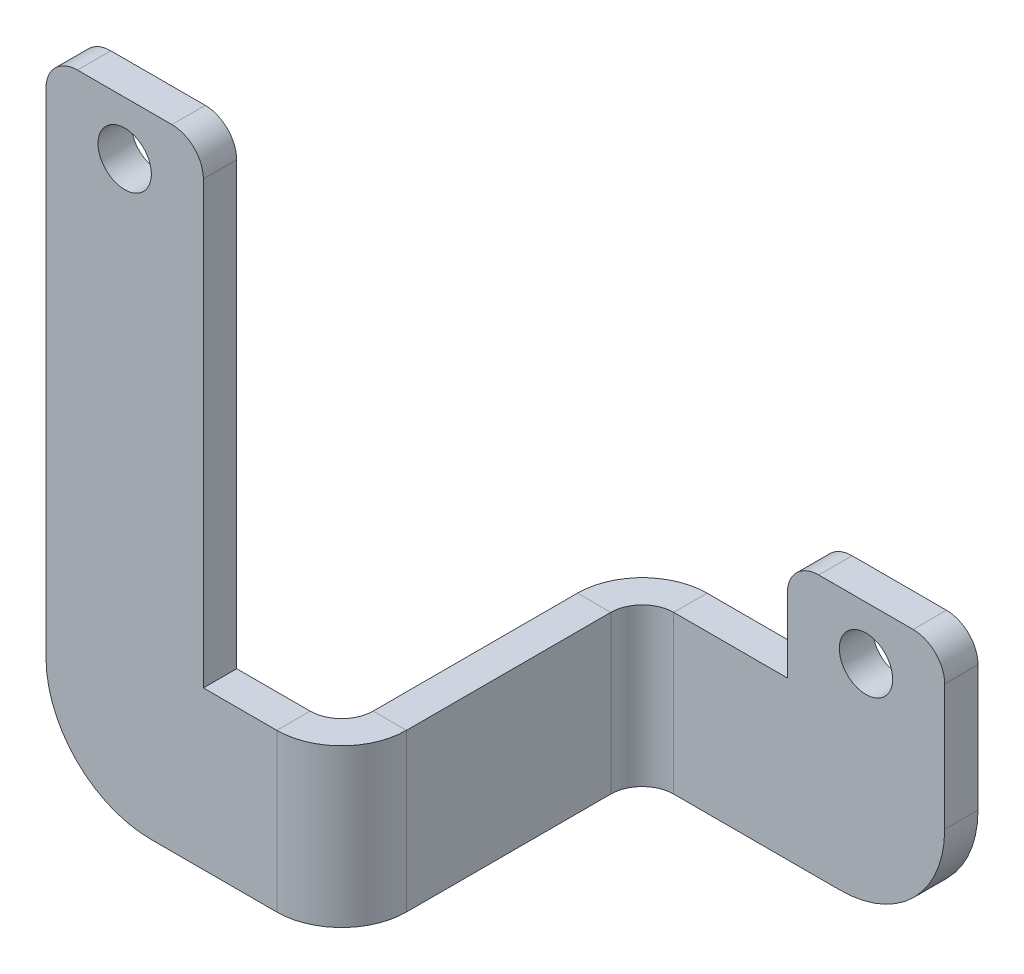
SolidWorks part; units mm, degrees
note: The reader was unsure of these and kept them because the rebuilt part matched: flange length of "Edge-Flange1", "Edge-Flange2".
material "Custom Plastic"
ref_plane "X-Y Datum" through (0, 0, 0) normal (0, 0, 1) x (1, 0, 0)
ref_plane "X-Z Datum" through (0, 0, 0) normal (0, 1, 0) x (1, 0, 0)
ref_plane "Y-Z Datum" through (0, 0, 0) normal (1, 0, 0) x (0, 0, -1)
sketch "Sketch1" plane through (0, 0, 0) normal (0, 0, 1) x (1, 0, 0)
  line L1 (-12.5, -7.5) -> (12.5, -7.5)
  line L2 (-12.5, -7.5) -> (-12.5, 7.5)
  line L3 (-12.5, 7.5) -> (12.5, 7.5)
  line L4 (12.5, -7.5) -> (12.5, 7.5)
  line L5 (-12.5, -7.5) -> (12.5, 7.5) construction
  line L6 (-12.5, 7.5) -> (12.5, -7.5) construction
  point P0 (0, 0)
  dimension "D1" = 25
  dimension "D2" = 15
base flange "Base-Flange1" sketch "Sketch1" thickness 3.175 reverse thickness direction no parameters "D1"=10
edge flange "Edge-Flange1" sketch "Sketch8" flange angle 90 flange length 28.65 flange position material outside bend radius 3 thickness 3.175 parameters "D6"=10
sketch "Sketch8" plane through (12.5, 0, -3.175) normal (-1, 0, 0) x (0, 1, 0)
  line L2 (-7.5, 0) -> (-7.5, 25.475)
  line L3 (-7.5, 25.475) -> (7.5, 25.475)
  line L4 (7.5, 25.475) -> (7.5, 0)
  line L5 (7.5, 0) -> (-7.5, 0) construction
  line L6 (7.5, 0) -> (-7.5, 0)
bend "EdgeBend1" bend radius 3 bend angle 90 parameters "D5"=1
edge flange "Edge-Flange2" sketch "Sketch11" flange angle 90 flange length 32 flange position material outside bend radius 3 thickness 3.175 parameters "D6"=10
sketch "Sketch11" plane through (15.675, 0, -28.65) normal (0, 0, 1) x (0, -1, 0)
  line L2 (-7.5, 0) -> (-7.5, 28.825)
  line L3 (-7.5, 28.825) -> (7.5, 28.825)
  line L4 (7.5, 28.825) -> (7.5, 0)
  line L5 (7.5, 0) -> (-7.5, 0) construction
  line L6 (7.5, 0) -> (-7.5, 0)
bend "EdgeBend2" bend radius 3 bend angle 90 parameters "D5"=2
sketch "Sketch12" plane through (0, 7.5, 0) normal (0, 1, 0) x (1, 0, 0)
  line L0 (9.5, 0) -> (-12.5, 0) construction
  line L1 (-12.5, 3.175) -> (2.5, 3.175)
  line L2 (-12.5, 3.175) -> (-12.5, 0)
  line L3 (-12.5, 0) -> (2.5, 0)
  line L4 (2.5, 3.175) -> (2.5, 0)
  dimension "D1" = 15
extrude "Boss-Extrude1" add sketch "Sketch12" along normal blind 45
sketch "Sketch15" plane through (0, 0, -3.175) normal (0, 0, -1) x (-1, 0, 0)
  line L0 (5, 52.5) -> (5, 47.42)
  line L3 (-2.5, 52.5) -> (12.5, 52.5) construction
  circle A2 centre (5, 47.42) radius 2.54
  dimension "D1" = 5.08
extrude "Cut-Extrude2" cut sketch "Sketch15" against normal through all
sketch "Sketch19" plane through (0, 7.5, 0) normal (0, 1, 0) x (1, 0, 0)
  line L0 (44.5, 28.65) -> (18.675, 28.65) construction
  line L1 (44.5, 31.825) -> (29.5, 31.825)
  line L2 (44.5, 31.825) -> (44.5, 28.65)
  line L3 (44.5, 28.65) -> (29.5, 28.65)
  line L4 (29.5, 31.825) -> (29.5, 28.65)
  dimension "D1" = 15
extrude "Boss-Extrude2" add sketch "Sketch19" along normal blind 10
sketch "Sketch21" plane through (0, 0, -31.825) normal (0, 0, -1) x (-1, 0, 0)
  line L0 (-37, 17.5) -> (-37, 12.42)
  line L2 (-44.5, 17.5) -> (-29.5, 17.5) construction
  circle A1 centre (-37, 12.42) radius 2.54
extrude "Cut-Extrude3" cut sketch "Sketch21" against normal through all
fillet "Fillet2" radius 3 4 edges at (29.5, 17.5, -30.2375) (44.5, 17.5, -30.2375) (2.5, 52.5, -1.5875) (-12.5, 52.5, -1.5875)
fillet "Fillet3" radius 10 2 edges at (44.5, -7.5, -30.2375) (-12.5, -7.5, -1.5875)
sketch "Bend-Lines1" [suppressed] plane through (0, 0, 0) normal (0, 1, 0) x (1, 0, 0)
sketch "Bounding-Box1" [suppressed] plane through (0, 0, 0) normal (0, 1, 0) x (1, 0, 0)
sheet metal parameters "Sheet-Metal1" thickness 3.175 parameters "D1"=10
flat pattern "Flat-Pattern1" [suppressed]
sketch "Bend-Lines2" plane through (0, 0, 0) normal (0, 1, 0) x (1, 0, 0)
sketch3d "Bounding-Box2" [suppressed]
  line L0 (15, -7.5, 0) -> (-15, -7.5, 0) construction
  line L1 (15, 7.5, 0) -> (-15, 7.5, 0) construction
  line L2 (15, -7.5, 0) -> (15, 7.5, 0) construction
  line L3 (-15, -7.5, 0) -> (-15, 7.5, 0) construction
sheet metal parameters "Sheet-Metal2" thickness 3.175 parameters "D1"=10
flat pattern "Flat-Pattern1"
sketch "Bend-Lines2" plane through (0, 0, 0) normal (0, 0, 1) x (1, 0, 0)
  line L0 (15.603, -7.5) -> (15.603, 7.5) construction
  line L1 (15.603, -7.5) -> (15.603, 7.5) construction
sketch3d "Bounding-Box2" [suppressed]
  line L0 (-15, -7.5, 0) -> (38.031, -7.5, 0) construction
  line L1 (-15, 7.5, 0) -> (38.031, 7.5, 0) construction
  line L2 (-15, -7.5, 0) -> (-15, 7.5, 0) construction
  line L3 (38.031, -7.5, 0) -> (38.031, 7.5, 0) construction
bend of the flat pattern "Flatten-<EdgeBend1>1"
sheet metal parameters "Sheet-Metal3" thickness 3.175 parameters "D1"=10
flat pattern "Flat-Pattern1"
sketch "Bend-Lines2" plane through (0, 0, 0) normal (0, 0, 1) x (1, 0, 0)
  line L0 (23.103, -7.5) -> (23.103, 7.5) construction
  line L1 (23.103, -7.5) -> (23.103, 7.5) construction
  line L2 (46.134, -7.5) -> (46.134, 7.5) construction
  line L3 (46.134, -7.5) -> (46.134, 7.5) construction
sketch3d "Bounding-Box2" [suppressed]
  line L0 (-22.5, -7.5, 0) -> (73.5621, -7.5, 0) construction
  line L1 (-22.5, 7.5, 0) -> (73.5621, 7.5, 0) construction
  line L2 (-22.5, -7.5, 0) -> (-22.5, 7.5, 0) construction
  line L3 (73.5621, -7.5, 0) -> (73.5621, 7.5, 0) construction
bend of the flat pattern "Flatten-<EdgeBend1>1"
bend of the flat pattern "Flatten-<EdgeBend2>1"
sheet metal parameters "Sheet-Metal4" thickness 3.175 parameters "D1"=10
flat pattern "Flat-Pattern1"
sketch "Bend-Lines2" plane through (0, 0, 0) normal (0, 0, 1) x (1, 0, 0)
  line L0 (20.603, -7.5) -> (20.603, 7.5) construction
  line L1 (20.603, -7.5) -> (20.603, 7.5) construction
  line L2 (53.634, -7.5) -> (53.634, 7.5) construction
  line L3 (53.634, -7.5) -> (53.634, 7.5) construction
sketch3d "Bounding-Box2" [suppressed]
  line L0 (-20, -7.5, 0) -> (81.0621, -7.5, 0) construction
  line L1 (-20, 41.5, 0) -> (81.0621, 41.5, 0) construction
  line L2 (-20, -7.5, 0) -> (-20, 41.5, 0) construction
  line L3 (81.0621, -7.5, 0) -> (81.0621, 41.5, 0) construction
bend of the flat pattern "Flatten-<EdgeBend1>1"
bend of the flat pattern "Flatten-<EdgeBend2>1"
sheet metal parameters "Sheet-Metal6" thickness 3.175 parameters "D1"=10
flat pattern "Flat-Pattern1" [suppressed]
sketch "Bend-Lines2" plane through (0, 0, 0) normal (0, 0, 1) x (1, 0, 0)
  line L0 (25.603, -10) -> (25.603, 10) construction
  line L1 (25.603, -10) -> (25.603, 10) construction
  line L2 (51.634, -10) -> (51.634, 10) construction
  line L3 (51.634, -10) -> (51.634, 10) construction
sketch3d "Bounding-Box2" [suppressed]
  line L0 (-25, -10, 0) -> (74.0621, -10, 0) construction
  line L1 (-25, 32, 0) -> (74.0621, 32, 0) construction
  line L2 (-25, -10, 0) -> (-25, 32, 0) construction
  line L3 (74.0621, -10, 0) -> (74.0621, 32, 0) construction
bend of the flat pattern "Flatten-<EdgeBend1>1"
bend of the flat pattern "Flatten-<EdgeBend2>1"
sketch "Sketch14-1" [suppressed] plane through (24.0621, 0, -3.175) normal (0, 0, -1) x (-1, 0, 0)
  line L0 (-50, 0) -> (-44.92, 0)
  circle A0 centre (-44.92, 0) radius 2.54
  dimension "D1" = 5.08
sheet metal parameters "Sheet-Metal7" thickness 3.175 parameters "D1"=10
flat pattern "Flat-Pattern1"
sketch "Bend-Lines2" plane through (0, 0, 0) normal (0, 0, 1) x (1, 0, 0)
  line L0 (23.103, -7.5) -> (23.103, 7.5) construction
  line L1 (23.103, -7.5) -> (23.103, 7.5) construction
  line L2 (49.134, -7.5) -> (49.134, 7.5) construction
  line L3 (49.134, -7.5) -> (49.134, 7.5) construction
sketch3d "Bounding-Box2" [suppressed]
  line L0 (-22.5, -7.5, 0) -> (76.5621, -7.5, 0) construction
  line L1 (-22.5, 31.5, 0) -> (76.5621, 31.5, 0) construction
  line L2 (-22.5, -7.5, 0) -> (-22.5, 31.5, 0) construction
  line L3 (76.5621, -7.5, 0) -> (76.5621, 31.5, 0) construction
bend of the flat pattern "Flatten-<EdgeBend1>1"
bend of the flat pattern "Flatten-<EdgeBend2>1"
sheet metal parameters "Sheet-Metal8" thickness 3.175 parameters "D1"=10
flat pattern "Flat-Pattern1"
sketch "Bend-Lines2" plane through (0, 0, 0) normal (0, 0, 1) x (1, 0, 0)
  line L0 (13.103, -7.5) -> (13.103, 7.5) construction
  line L1 (13.103, -7.5) -> (13.103, 7.5) construction
  line L2 (39.784, -7.5) -> (39.784, 7.5) construction
  line L3 (39.784, -7.5) -> (39.784, 7.5) construction
sketch3d "Bounding-Box2" [suppressed]
  line L0 (-12.5, -7.5, 0) -> (69.2121, -7.5, 0) construction
  line L1 (-12.5, 52.5, 0) -> (69.2121, 52.5, 0) construction
  line L2 (-12.5, -7.5, 0) -> (-12.5, 52.5, 0) construction
  line L3 (69.2121, -7.5, 0) -> (69.2121, 52.5, 0) construction
bend of the flat pattern "Flatten-<EdgeBend1>1"
bend of the flat pattern "Flatten-<EdgeBend2>1"
